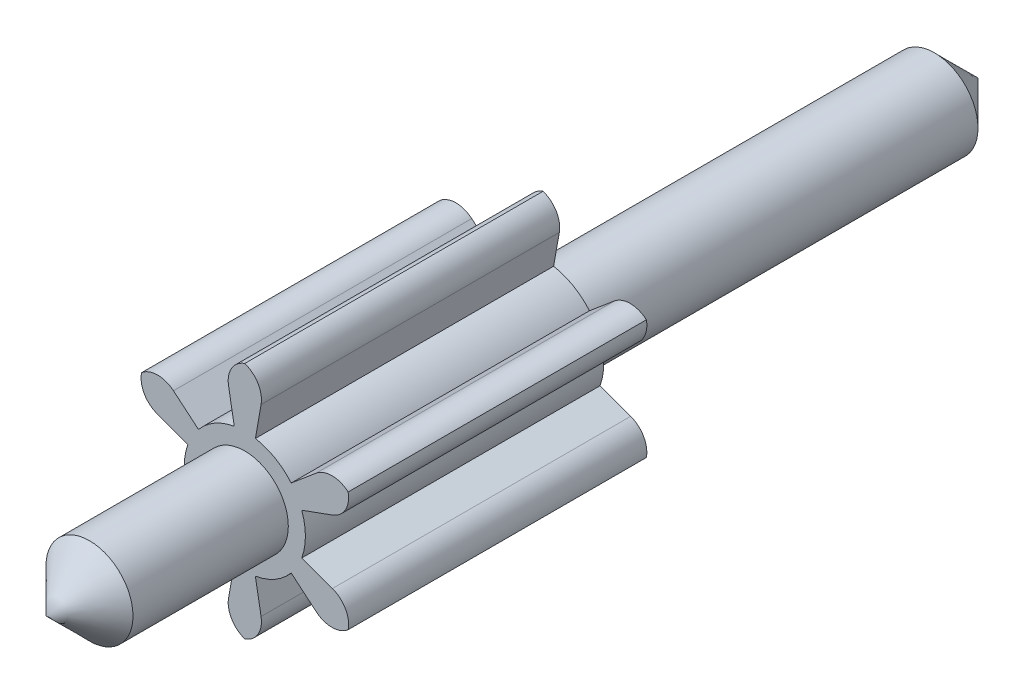
SolidWorks part; units mm, degrees
material "AISI 316 Stainless Steel Sheet (SS)"
ref_plane "Front Plane" through (0, 0, 0) normal (0, 0, 1) x (1, 0, 0)
ref_plane "Top Plane" through (0, 0, 0) normal (0, 1, 0) x (1, 0, 0)
ref_plane "Right Plane" through (0, 0, 0) normal (1, 0, 0) x (0, 0, -1)
sketch "Sketch2" plane through (0, 0, 0) normal (0, 0, 1) x (1, 0, 0)
  line L0 (0, -1.156) -> (0, 1.2341) construction
  line L1 (-0.085, 0.48) -> (-0.1307, 0.7385)
  line L2 (0.085, 0.48) -> (0.1307, 0.7385)
  line L3 (0.4582, 0.1664) -> (0.7049, 0.256)
  line L4 (0.3732, 0.3136) -> (0.5742, 0.4825)
  line L5 (0.3732, -0.3136) -> (0.5742, -0.4825)
  line L6 (0.4582, -0.1664) -> (0.7049, -0.256)
  line L7 (-0.085, -0.48) -> (-0.1307, -0.7385)
  line L8 (0.085, -0.48) -> (0.1307, -0.7385)
  line L9 (-0.4582, -0.1664) -> (-0.7049, -0.256)
  line L10 (-0.3732, -0.3136) -> (-0.5742, -0.4825)
  line L11 (-0.3732, 0.3136) -> (-0.5742, 0.4825)
  line L12 (-0.4582, 0.1664) -> (-0.7049, 0.256)
  arc A0 (-0.085, 0.48) -> (-0.3732, 0.3136) centre (0, 0) ccw
  arc A1 (-0.4582, 0.1664) -> (-0.4582, -0.1664) centre (0, 0) ccw
  arc A2 (0.3732, 0.3136) -> (0.085, 0.48) centre (0, 0) ccw
  arc A3 (-0.1307, 0.7385) -> (0, 0.96) centre (0.0639, 0.773) cw
  arc A4 (0.1307, 0.7385) -> (0, 0.96) centre (-0.0639, 0.773) ccw
  arc A5 (0.5742, 0.4825) -> (0.8314, 0.48) centre (0.7013, 0.3312) cw
  arc A6 (0.7049, 0.256) -> (0.8314, 0.48) centre (0.6375, 0.4418) ccw
  arc A7 (0.7049, -0.256) -> (0.8314, -0.48) centre (0.6375, -0.4418) cw
  arc A8 (0.5742, -0.4825) -> (0.8314, -0.48) centre (0.7013, -0.3312) ccw
  arc A9 (0.1307, -0.7385) -> (0, -0.96) centre (-0.0639, -0.773) cw
  arc A10 (-0.1307, -0.7385) -> (0, -0.96) centre (0.0639, -0.773) ccw
  arc A11 (-0.5742, -0.4825) -> (-0.8314, -0.48) centre (-0.7013, -0.3312) cw
  arc A12 (-0.7049, -0.256) -> (-0.8314, -0.48) centre (-0.6375, -0.4418) ccw
  arc A13 (-0.7049, 0.256) -> (-0.8314, 0.48) centre (-0.6375, 0.4418) cw
  arc A14 (-0.5742, 0.4825) -> (-0.8314, 0.48) centre (-0.7013, 0.3312) ccw
  arc A15 (0.4582, -0.1664) -> (0.4582, 0.1664) centre (0, 0) ccw
  arc A16 (0.085, -0.48) -> (0.3732, -0.3136) centre (0, 0) ccw
  arc A17 (-0.3732, -0.3136) -> (-0.085, -0.48) centre (0, 0) ccw
  circle A18 centre (0, 0) radius 0.35
  point P51 (0, 0)
  dimension "D1" = 1.92
  dimension "D2" = 0.975
  dimension "D3" = 0.7
  dimension "D4" = 6
extrude "Boss-Extrude2" add sketch "Sketch2" along normal blind 2.4
extrude "Boss-Extrude3" add sketch "Sketch2<2>" along normal blind 4 and the other way blind 3.5 contours A18 L0 | L0 A18 region at (-0.1485, 0, 0) region at (0.1485, 0, 0)
sketch "Sketch2<2>" plane through (0, 0, 0) normal (0, 0, 1) x (1, 0, 0) same geometry as "Sketch2"
chamfer "Chamfer1" distance 0.35 angle 45 2 edges at (0.35, 0, -3.5) (0.35, 0, 4)
